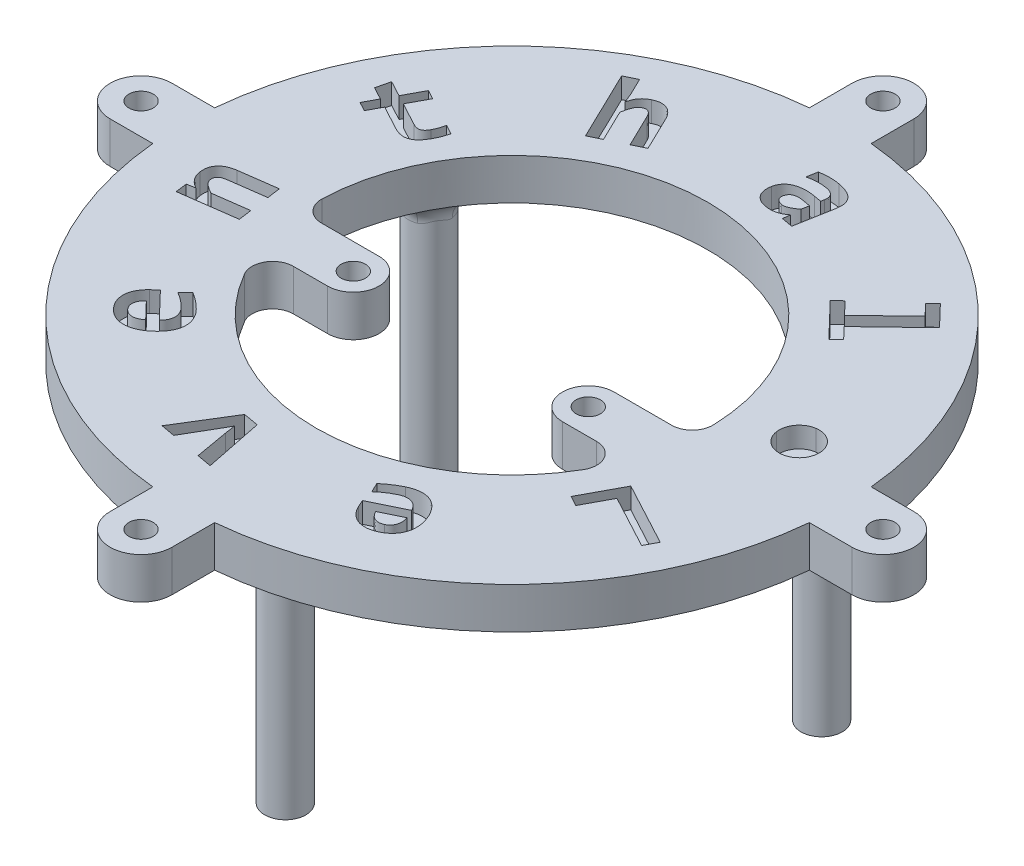
SolidWorks part; units mm, degrees
ref_plane "Front Plane" through (0, 0, 0) normal (0, 0, 1) x (1, 0, 0)
ref_plane "Top Plane" through (0, 0, 0) normal (0, 1, 0) x (1, 0, 0)
ref_plane "Right Plane" through (0, 0, 0) normal (1, 0, 0) x (0, 0, -1)
ref_axis "Center Axis" through (0, 0.65, 0) along (0, -1, 0)
sketch "STR Point" plane through (0, 0, 0) normal (0, 1, 0) x (1, 0, 0)
  point P0 (0.8, 2.9)
  dimension "D1" = 0.8
  dimension "D2" = 2.9
ref_axis "STR Axis" through (0.8, 0, -2.9) along (0, 1, 0)
sketch "Sketch1" plane through (0, 0, 0) normal (0, 1, 0) x (1, 0, 0)
  circle A0 centre (0, -11) radius 1
  dimension "D1" = 11
extrude "Boss-Extrude1" add sketch "Sketch1" against normal blind 13
sketch "Sketch2" plane through (0, 0, 0) normal (0, 1, 0) x (1, 0, 0)
  line L0 (5.7, -2) -> (9.2871, -2) construction
  line L1 (5.7, -0.75) -> (8.4963, -0.75)
  line L2 (5.7, -3.25) -> (7.3612, -3.25)
  line L3 (-18, 1.5) -> (-15.9295, 1.5)
  line L4 (-18, -1.5) -> (-15.9295, -1.5)
  line L5 (-5.7, -2) -> (-9.2871, -2) construction
  line L6 (-5.7, -3.25) -> (-7.3612, -3.25)
  line L7 (1.5, 18) -> (1.5, 15.9295)
  line L8 (-1.5, 18) -> (-1.5, 15.9295)
  line L9 (18, 1.5) -> (15.9295, 1.5)
  line L10 (18, -1.5) -> (15.9295, -1.5)
  line L11 (1.5, -18) -> (1.5, -15.9295)
  line L12 (-1.5, -18) -> (-1.5, -15.9295)
  line L13 (-5.7, -0.75) -> (-8.4963, -0.75)
  arc A0 (-15.9295, -1.5) -> (-1.5, -15.9295) centre (0, 0) ccw
  circle A1 centre (-5.7, -2) radius 0.59
  circle A2 centre (5.7, -2) radius 0.59
  arc A3 (-18, 1.5) -> (-18, -1.5) centre (-18, 0) ccw
  arc A4 (1.5, 18) -> (-1.5, 18) centre (0, 18) ccw
  arc A5 (18, -1.5) -> (18, 1.5) centre (18, 0) ccw
  arc A6 (-1.5, -18) -> (1.5, -18) centre (0, -18) ccw
  arc A7 (1.5, -15.9295) -> (15.9295, -1.5) centre (0, 0) ccw
  arc A8 (15.9295, 1.5) -> (1.5, 15.9295) centre (0, 0) ccw
  arc A9 (-1.5, 15.9295) -> (-15.9295, 1.5) centre (0, 0) ccw
  circle A10 centre (0, 18) radius 0.59
  circle A11 centre (18, 0) radius 0.59
  circle A12 centre (-18, 0) radius 0.59
  circle A13 centre (0, -18) radius 0.59
  arc A14 (-8.2272, -4.75) -> (8.2272, -4.75) centre (0, 0) ccw
  arc A15 (5.7, -0.75) -> (5.7, -3.25) centre (5.7, -2) ccw
  arc A16 (9.4959, 0.2794) -> (-9.4959, 0.2794) centre (0, 0) ccw
  arc A17 (-5.7, -3.25) -> (-5.7, -0.75) centre (-5.7, -2) ccw
  arc A18 (-7.3612, -3.25) -> (-8.2272, -4.75) centre (-7.3612, -4.25) ccw
  arc A19 (-8.4963, -0.75) -> (-9.4959, 0.2794) centre (-8.4963, 0.25) cw
  arc A20 (7.3612, -3.25) -> (8.2272, -4.75) centre (7.3612, -4.25) cw
  arc A21 (8.4963, -0.75) -> (9.4959, 0.2794) centre (8.4963, 0.25) ccw
  point P8 (7.4935, -2)
  point P37 (-7.4935, -2)
  point P50 (9.4703, -0.75)
  dimension "D1" = 5.7
  dimension "D2" = 2
  dimension "D5" = 1
  dimension "D4" = 1
  dimension "D3" = 5.7
extrude "Boss-Extrude2" add sketch "Sketch2" along normal blind 2
pattern_circular "CirPattern2" count 3 over 360 about axis through (0, 0.65, 0) along (0, -1, 0) of "Boss-Extrude1" reverse direction yes
fillet "Fillet1" radius 1 3 edges at (10.3923, 0, -6) (0, 0, 12) (-10.3923, 0, -6)
sketch "Sketch4" plane through (0, 2, 0) normal (0, 1, 0) x (1, 0, 0)
  circle A0 centre (0, 0) radius 11
sketch "Sketch3" plane through (0, 2, 0) normal (0, 1, 0) x (1, 0, 0)
  text T0 "Leventhal•" font "Consolas" height 3.5
extrude "Cut-Extrude1" cut sketch "Sketch3" against normal blind 1
